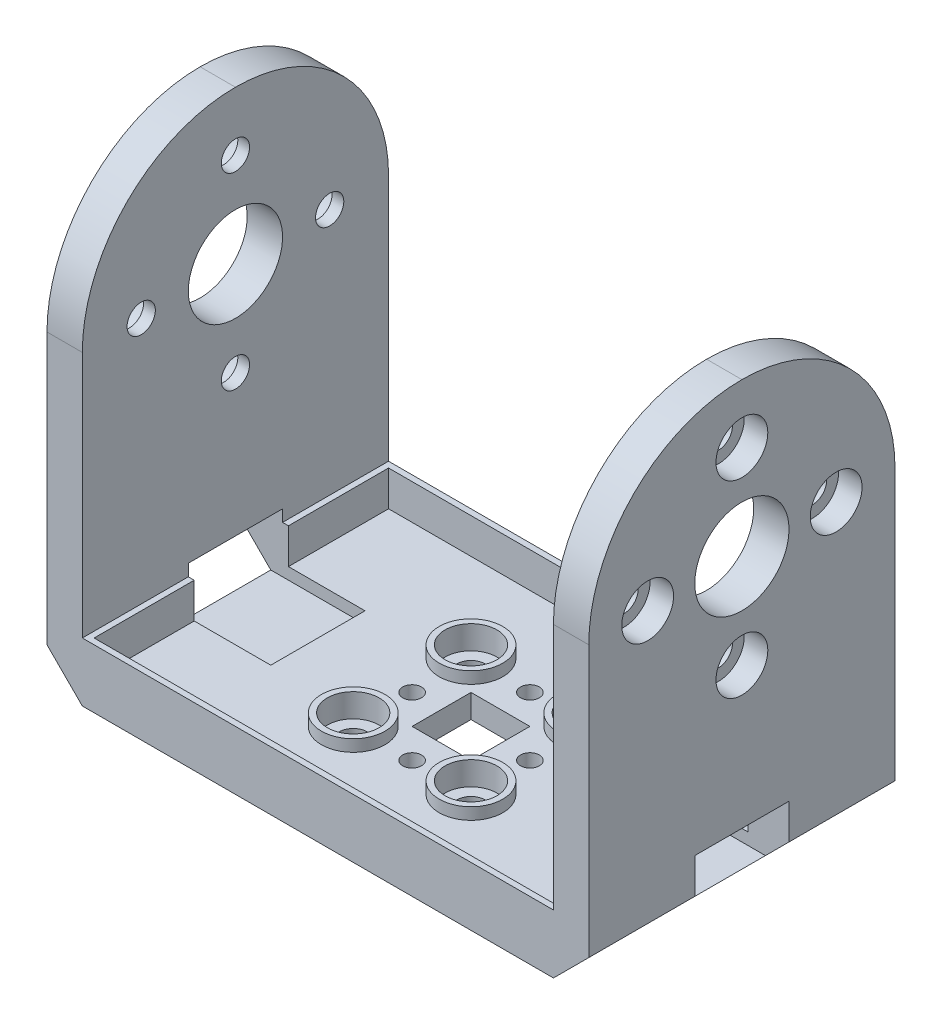
SolidWorks part; units mm, degrees
ref_plane "Front" through (0, 0, 0) normal (0, 0, 1) x (1, 0, 0)
ref_plane "Top" through (0, 0, 0) normal (0, 1, 0) x (1, 0, 0)
ref_plane "Right" through (0, 0, 0) normal (1, 0, 0) x (0, 0, -1)
sketch "草图1" plane through (0, 0, 0) normal (0, 1, 0) x (1, 0, 0)
  line L1 (-23, 13) -> (23, 13)
  line L2 (-23, 13) -> (-23, -13)
  line L3 (-23, -13) -> (23, -13)
  line L4 (23, 13) -> (23, -13)
  line L5 (-23, 13) -> (23, -13) construction
  line L6 (-23, -13) -> (23, 13) construction
  point P0 (0, 0)
  dimension "D1" = 46
  dimension "D2" = 26
extrude "凸台-拉伸1" add sketch "草图1" along normal blind 5
sketch "草图2" plane through (0, 5, 0) normal (0, 1, 0) x (1, 0, 0)
  line L0 (-23, -13) -> (23, -13) construction
  line L1 (-23, 13) -> (-20, 13)
  line L2 (-23, 13) -> (-23, -13)
  line L3 (-23, -13) -> (-20, -13)
  line L4 (-20, 13) -> (-20, -13)
  line L6 (23, 13) -> (20, 13)
  line L7 (23, 13) -> (23, -13)
  line L8 (23, -13) -> (20, -13)
  line L9 (20, 13) -> (20, -13)
  dimension "D1" = 3
  dimension "D2" = 3
extrude "凸台-拉伸2" add sketch "草图2" along normal blind 34
fillet "圆角1" radius 13 4 edges at (21.5, 39, -13) (-21.5, 39, -13) (21.5, 39, 13) (-21.5, 39, 13)
sketch "草图3" plane through (-23, 0, 0) normal (-1, 0, 0) x (0, 0, 1)
  line L0 (-13, 26) -> (13, 26) construction
  circle A0 centre (0, 26) radius 4
  dimension "D1" = 8
extrude "切除-拉伸1" cut sketch "草图3" against normal up to next
sketch "草图4" plane through (-23, 0, 0) normal (-1, 0, 0) x (0, 0, 1)
  line L0 (-13, 26) -> (13, 26) construction
  line L1 (0, 39) -> (0, 15.0372) construction
  point P9 (-8, 26)
  point P10 (0, 34)
  point P11 (8, 26)
  point P12 (0, 18)
  dimension "D1" = 8
  dimension "D2" = 8
  dimension "D3" = 8
  dimension "D4" = 8
hole_wizard "M2 凹头盖螺钉的柱形沉头孔1" positions "3D草图1" profile "草图5" counterbore size "M2" standard "ANSI Metric" end condition through all
sketch3d "3D草图1"
  point P0 (-23, 26, -8)
  point P3 (-23, 34, 0)
  point P6 (-23, 26, 8)
  point P9 (-23, 18, 0)
sketch "草图5" plane through (-23, 26, -8) normal (0, 1, 0) x (0, 0, 1)
  line L0 (0, 0) -> (0, 46)
  line L1 (0, 46) -> (1.2, 46)
  line L3 (1.2, 46) -> (1.2, 2)
  line L4 (1.2, 2) -> (2.2, 2)
  line L5 (2.2, 2) -> (2.2, 0)
  line L7 (2.2, 0) -> (0, 0)
  line L11 (0, -6.35) -> (0, 107.95) construction
  dimension "通孔孔直径" = 2.4
  dimension "通孔孔深度" = 46
  dimension "柱形沉头孔直径" = 4.4
  dimension "柱形沉头孔深度" = 2
mirror "镜向1" about plane through (0, 0, 0) normal (1, 0, 0) of "切除-拉伸1", "M2 凹头盖螺钉的柱形沉头孔1"
sketch "草图6" plane through (0, 5, 0) normal (0, 1, 0) x (1, 0, 0)
  line L8 (-19.5, -12.5) -> (19.5, -12.5)
  line L9 (19.5, -12.5) -> (19.5, 12.5)
  line L14 (19.5, 12.5) -> (-19.5, 12.5)
  line L15 (-19.5, 12.5) -> (-19.5, -12.5)
  line L16 (-19.5, -12.5) -> (19.5, -12.5)
  line L17 (19.5, -12.5) -> (19.5, 12.5)
  line L18 (19.5, 12.5) -> (-19.5, 12.5)
  line L19 (-19.5, 12.5) -> (-19.5, -12.5)
  dimension "D1" = 0.5
extrude "切除-拉伸3" cut sketch "草图6" against normal blind 3
chamfer "倒角1" distance 3 angle 45 2 edges at (23, 0, 0) (-23, 0, 0)
sketch "草图7" plane through (23, 0, 0) normal (1, 0, 0) x (0, 0, -1)
  line L0 (0, 0) -> (0, 7.8797) construction
  line L1 (13, 0) -> (-13, 0) construction
  line L2 (-4, 6) -> (4, 6)
  line L3 (-4, 6) -> (-4, 1)
  line L4 (-4, 1) -> (4, 1)
  line L5 (4, 6) -> (4, 1)
  line L6 (-4, 6) -> (4, 1) construction
  line L7 (-4, 1) -> (4, 6) construction
  point P3 (0, 3.5)
  dimension "D1" = 8
  dimension "D2" = 5
  dimension "D3" = 1
extrude "切除-拉伸4" cut sketch "草图7" against normal blind 10
mirror "镜向2" about plane through (0, 0, 0) normal (1, 0, 0) of "切除-拉伸4"
sketch "草图8" plane through (0, 2, 0) normal (0, 1, 0) x (1, 0, 0)
  line L1 (-2.5, 2.5) -> (2.5, 2.5)
  line L2 (-2.5, 2.5) -> (-2.5, -2.5)
  line L3 (-2.5, -2.5) -> (2.5, -2.5)
  line L4 (2.5, 2.5) -> (2.5, -2.5)
  line L5 (-2.5, 2.5) -> (2.5, -2.5) construction
  line L6 (-2.5, -2.5) -> (2.5, 2.5) construction
  point P0 (0, 0)
  dimension "D1" = 5
  dimension "D2" = 5
extrude "切除-拉伸5" cut sketch "草图8" against normal blind 10
sketch "草图9" plane through (0, 2, 0) normal (0, 1, 0) x (1, 0, 0)
  circle A0 centre (-5, 5) radius 2.7
  circle A2 centre (5, 5) radius 2.7
  circle A6 centre (5, -5) radius 2.7
  circle A8 centre (-5, -5) radius 2.7
  circle A9 centre (0, 0) radius 2.7 [skipped]
  arc A10 (-5, -2.7) -> (-5, 2.7) centre (-5, 0) ccw [skipped]
  arc A11 (2.7, 5) -> (-2.7, 5) centre (0, 5) ccw [skipped]
  arc A12 (5, -2.7) -> (5, 2.7) centre (5, 0) ccw [skipped]
  arc A13 (-2.7, -5) -> (2.7, -5) centre (0, -5) ccw [skipped]
  point P8 (0, 0)
  line M17 (13, -4) -> (13, 4)
  dimension "D1" = 5.4
  dimension "D2" = 3
  dimension "D3" = 3
extrude "凸台-拉伸7" add sketch "草图9" along normal blind 1 contours A8 | A6 | A0 | A2 M17 | A8 region at (-5, 2, -5) region at (5, 2, -5) region at (5, 2, 5) region at (-5, 2, 5)
sketch "草图10" plane through (0, 3, 0) normal (0, 1, 0) x (1, 0, 0)
  point P0 (-5, 5)
  point P1 (5, 5)
  point P3 (5, -5)
  point P5 (-5, -5)
hole_wizard "M2 凹头盖螺钉的柱形沉头孔2" positions "3D草图2" profile "草图11" counterbore size "M2" standard "ANSI Metric" end condition through all
sketch3d "3D草图2"
  point P0 (-5, 3, 5)
  point P3 (5, 3, 5)
  point P6 (5, 3, -5)
  point P9 (-5, 3, -5)
sketch "草图11" plane through (-5, 3, 5) normal (1, 0, 0) x (0, 0, 1)
  line L0 (0, 0) -> (0, 3)
  line L1 (0, 3) -> (1.2, 3)
  line L3 (1.2, 3) -> (1.2, 2)
  line L4 (1.2, 2) -> (2.2, 2)
  line L5 (2.2, 2) -> (2.2, 0)
  line L7 (2.2, 0) -> (0, 0)
  line L11 (0, -6.35) -> (0, 107.95) construction
  dimension "通孔孔直径" = 2.4
  dimension "通孔孔深度" = 3
  dimension "柱形沉头孔直径" = 4.4
  dimension "柱形沉头孔深度" = 2
sketch "草图12" plane through (0, 2, 0) normal (0, 1, 0) x (1, 0, 0)
  point P0 (-5, 0)
  point P1 (0, 5)
  point P2 (5, 0)
  point P3 (0, -5)
hole_wizard "M2x0.4 螺纹孔1" positions "3D草图3" profile "草图13" tap size "M2x0.4" standard "ANSI Metric" end condition through all
sketch3d "3D草图3"
  point P0 (-5, 2, 0)
  point P3 (0, 2, -5)
  point P6 (5, 2, 0)
  point P9 (0, 2, 5)
sketch "草图13" plane through (-5, 2, 0) normal (1, 0, 0) x (0, 0, 1)
  line L0 (0, 0) -> (0, 2)
  line L1 (0, 2) -> (0.8, 2)
  line L2 (0.8, 2) -> (0.8, 0)
  line L5 (0.8, 0) -> (0, 0)
  line L11 (0, -6.35) -> (0, 107.95) construction
  dimension "通孔螺纹孔钻头直径" = 1.6
  dimension "通孔螺纹孔钻头深度" = 2
cosmetic thread "孔螺蚊线1" parameters "D2"=2
cosmetic thread "孔螺蚊线2" parameters "D2"=2
cosmetic thread "孔螺蚊线3" parameters "D2"=2
cosmetic thread "孔螺蚊线4" parameters "D2"=2
